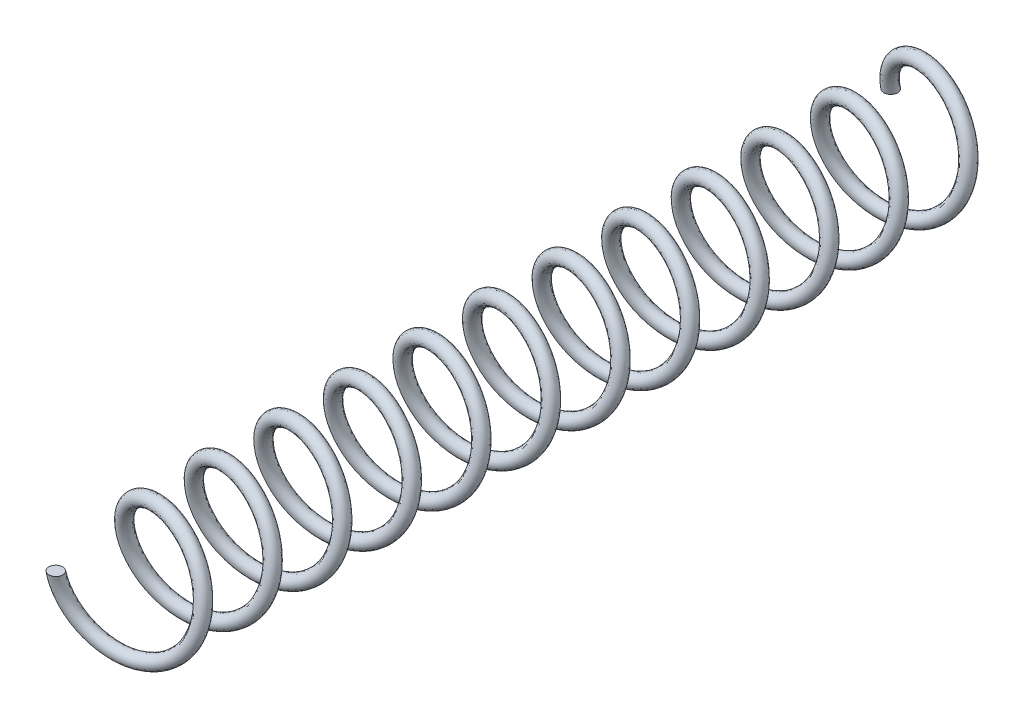
SolidWorks part; units mm, degrees
ref_plane "前视基准面" through (0, 0, 0) normal (0, 0, 1) x (1, 0, 0)
ref_plane "上视基准面" through (0, 0, 0) normal (0, 1, 0) x (1, 0, 0)
ref_plane "右视基准面" through (0, 0, 0) normal (1, 0, 0) x (0, 0, -1)
sketch "草图1" plane through (0, 0, 0) normal (0, 0, 1) x (1, 0, 0)
  circle A0 centre (0, 0) radius 4
curve "螺旋线/涡状线1" pitch 5 height 60 turns 12
sketch "草图3" plane through (0, 0, 0) normal (0, 1, 0) x (1, 0, 0)
  circle A0 centre (-4, 0) radius 0.5
  spline S0 degree 3 poles (-4, 0) (-4, -0.1035) (-3.7917, -0.3128) (-2.9021, -0.6249) (-1.5706, -0.9375) (0, -1.25) (1.5706, -1.5625) (2.9021, -1.875) (3.7917, -2.1875) (4.1041, -2.5) (3.7917, -2.8125) (2.9021, -3.125) (1.1268, -3.5417) (-1.1268, -3.9583) (-2.9021, -4.375) (-3.7917, -4.6875) (-4.1041, -5) (-3.7917, -5.3125) (-2.9021, -5.625) (-1.1268, -6.0417) (1.1268, -6.4583) (2.9021, -6.875) (3.7917, -7.1875) (4.1041, -7.5) (3.7917, -7.8125) (2.9021, -8.125) (1.1268, -8.5417) (-1.1268, -8.9583) (-2.9021, -9.375) (-3.7917, -9.6875) (-4.1041, -10) (-3.7917, -10.3125) (-2.9021, -10.625) (-1.1268, -11.0417) (1.1268, -11.4583) (2.9021, -11.875) (3.7917, -12.1875) (4.1041, -12.5) (3.7917, -12.8125) (2.9021, -13.125) (1.1268, -13.5417) (-1.1268, -13.9583) (-2.9021, -14.375) (-3.7917, -14.6875) (-4.1041, -15) (-3.7917, -15.3125) (-2.9021, -15.625) (-1.1268, -16.0417) (1.1268, -16.4583) (2.9021, -16.875) (3.7917, -17.1875) (4.1041, -17.5) (3.7917, -17.8125) (2.9021, -18.125) (1.1268, -18.5417) (-1.1268, -18.9583) (-2.9021, -19.375) (-3.7917, -19.6875) (-4.1041, -20) (-3.7917, -20.3125) (-2.9021, -20.625) (-1.1268, -21.0417) (1.1268, -21.4583) (2.9021, -21.875) (3.7917, -22.1875) (4.1041, -22.5) (3.7917, -22.8125) (2.9021, -23.125) (1.1268, -23.5417) (-1.1268, -23.9583) (-2.9021, -24.375) (-3.7917, -24.6875) (-4.1041, -25) (-3.7917, -25.3125) (-2.9021, -25.625) (-1.1268, -26.0417) (1.1268, -26.4583) (2.9021, -26.875) (3.7917, -27.1875) (4.1041, -27.5) (3.7917, -27.8125) (2.9021, -28.125) (1.1268, -28.5417) (-1.1268, -28.9583) (-2.9021, -29.375) (-3.7917, -29.6875) (-4.1041, -30) (-3.7917, -30.3125) (-2.9021, -30.625) (-1.1268, -31.0417) (1.1268, -31.4583) (2.9021, -31.875) (3.7917, -32.1875) (4.1041, -32.5) (3.7917, -32.8125) (2.9021, -33.125) (1.1268, -33.5417) (-1.1268, -33.9583) (-2.9021, -34.375) (-3.7917, -34.6875) (-4.1041, -35) (-3.7917, -35.3125) (-2.9021, -35.625) (-1.1268, -36.0417) (1.1268, -36.4583) (2.9021, -36.875) (3.7917, -37.1875) (4.1041, -37.5) (3.7917, -37.8125) (2.9021, -38.125) (1.1268, -38.5417) (-1.1268, -38.9583) (-2.9021, -39.375) (-3.7917, -39.6875) (-4.1041, -40) (-3.7917, -40.3125) (-2.9021, -40.625) (-1.1268, -41.0417) (1.1268, -41.4583) (2.9021, -41.875) (3.7917, -42.1875) (4.1041, -42.5) (3.7917, -42.8125) (2.9021, -43.125) (1.1268, -43.5417) (-1.1268, -43.9583) (-2.9021, -44.375) (-3.7917, -44.6875) (-4.1041, -45) (-3.7917, -45.3125) (-2.9021, -45.625) (-1.1268, -46.0417) (1.1268, -46.4583) (2.9021, -46.875) (3.7917, -47.1875) (4.1041, -47.5) (3.7917, -47.8125) (2.9021, -48.125) (1.1268, -48.5417) (-1.1268, -48.9583) (-2.9021, -49.375) (-3.7917, -49.6875) (-4.1041, -50) (-3.7917, -50.3125) (-2.9021, -50.625) (-1.1268, -51.0417) (1.1268, -51.4583) (2.9021, -51.875) (3.7917, -52.1875) (4.1041, -52.5) (3.7917, -52.8125) (2.9021, -53.125) (1.1268, -53.5417) (-1.1268, -53.9583) (-2.9021, -54.375) (-3.7917, -54.6875) (-4.1041, -55) (-3.7917, -55.3125) (-2.9021, -55.625) (-1.1268, -56.0417) (1.1268, -56.4583) (2.9021, -56.875) (3.7917, -57.1875) (4.1041, -57.5) (3.7917, -57.8125) (2.9021, -58.125) (1.5706, -58.4375) (0, -58.75) (-1.5706, -59.0625) (-2.9021, -59.3751) (-3.7917, -59.6872) (-4, -59.8965) (-4, -60) knots 0 0 0 0 0.005208 0.010417 0.015625 0.020833 0.026042 0.03125 0.036458 0.041667 0.046875 0.052083 0.057292 0.067708 0.072917 0.078125 0.083333 0.088542 0.09375 0.098958 0.109375 0.114583 0.119792 0.125 0.130208 0.135417 0.140625 0.151042 0.15625 0.161458 0.166667 0.171875 0.177083 0.182292 0.192708 0.197917 0.203125 0.208333 0.213542 0.21875 0.223958 0.234375 0.239583 0.244792 0.25 0.255208 0.260417 0.265625 0.276042 0.28125 0.286458 0.291667 0.296875 0.302083 0.307292 0.317708 0.322917 0.328125 0.333333 0.338542 0.34375 0.348958 0.359375 0.364583 0.369792 0.375 0.380208 0.385417 0.390625 0.401042 0.40625 0.411458 0.416667 0.421875 0.427083 0.432292 0.442708 0.447917 0.453125 0.458333 0.463542 0.46875 0.473958 0.484375 0.489583 0.494792 0.5 0.505208 0.510417 0.515625 0.526042 0.53125 0.536458 0.541667 0.546875 0.552083 0.557292 0.567708 0.572917 0.578125 0.583333 0.588542 0.59375 0.598958 0.609375 0.614583 0.619792 0.625 0.630208 0.635417 0.640625 0.651042 0.65625 0.661458 0.666667 0.671875 0.677083 0.682292 0.692708 0.697917 0.703125 0.708333 0.713542 0.71875 0.723958 0.734375 0.739583 0.744792 0.75 0.755208 0.760417 0.765625 0.776042 0.78125 0.786458 0.791667 0.796875 0.802083 0.807292 0.817708 0.822917 0.828125 0.833333 0.838542 0.84375 0.848958 0.859375 0.864583 0.869792 0.875 0.880208 0.885417 0.890625 0.901042 0.90625 0.911458 0.916667 0.921875 0.927083 0.932292 0.942708 0.947917 0.953125 0.958333 0.963542 0.96875 0.973958 0.979167 0.984375 0.989583 0.994792 1 1 1 1 construction
  dimension "D1" = 1
sweep "扫描2" add profiles "草图3" path "螺旋线/涡状线1"
sketch "草图4" plane through (0, 0, 0) normal (0, 0, 1) x (1, 0, 0)
  circle A0 centre (0, 0) radius 5
